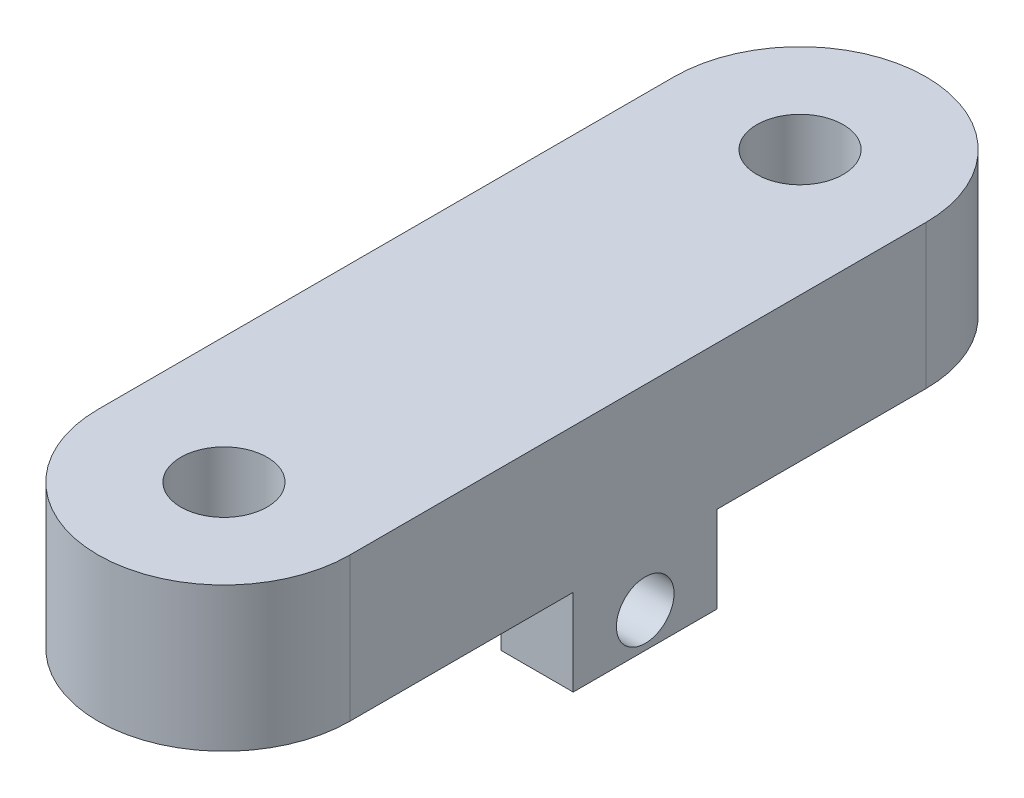
SolidWorks part; units mm, degrees
ref_plane "Front Plane" through (0, 0, 0) normal (0, 0, 1) x (1, 0, 0)
ref_plane "Top Plane" through (0, 0, 0) normal (0, 1, 0) x (1, 0, 0)
ref_plane "Right Plane" through (0, 0, 0) normal (1, 0, 0) x (0, 0, -1)
sketch "Sketch1" plane through (0, 0, 0) normal (0, 1, 0) x (1, 0, 0)
  line L0 (-12.5, 0) -> (-12.5, 10)
  line L1 (-12.5, 10) -> (-17.5, 10)
  line L2 (-17.5, 0) -> (-12.5, 0)
  line L3 (-17.5, 10) -> (-17.5, 0)
  line L4 (-5, 10) -> (0, 10)
  line L5 (-5, 10) -> (-5, 0)
  line L6 (-5, 0) -> (0, 0)
  line L7 (0, 10) -> (0, 0)
  point P8 (0, 0)
  point P9 (0, 0)
  dimension "D1" = 5
  dimension "D2" = 5
  dimension "D3" = 7.5
  dimension "D4" = 10
extrude "Boss-Extrude1" add sketch "Sketch1" along normal blind 6
sketch "Sketch2" plane through (0, 0, 0) normal (1, 0, 0) x (0, 0, -1)
  line L0 (0, 6) -> (0, 0) construction
  line L1 (0, 0) -> (10, 0) construction
  circle A0 centre (5, 2.43) radius 2
  point P2 (0, 0)
  dimension "D1" = 4
  dimension "D2" = 5
  dimension "D3" = 2.43
extrude "Cut-Extrude1" cut sketch "Sketch2" against normal blind 100
sketch "Sketch4" plane through (0, 6, 0) normal (0, 1, 0) x (1, 0, 0)
  line L0 (-17.5, -15.5) -> (-17.5, 24.5)
  line L3 (0, -15.5) -> (0, 24.5)
  line L4 (-17.5, 10) -> (-17.5, 0) construction
  arc A0 (-17.5, 24.5) -> (0, 24.5) centre (-8.75, 24.5) cw
  arc A1 (-17.5, -15.5) -> (0, -15.5) centre (-8.75, -15.5) ccw
  circle A2 centre (-8.75, 24.5) radius 3
  circle A3 centre (-8.75, -15.5) radius 3
  point P3 (-17.5, 4.5)
  point P6 (0, 4.5)
  point P13 (0, 0)
  point P14 (-8.75, 33.25)
  dimension "D2" = 6
  dimension "D3" = 20
  dimension "D4" = 20
  dimension "D1" = 20
extrude "Boss-Extrude2" add sketch "Sketch4" along normal blind 10
